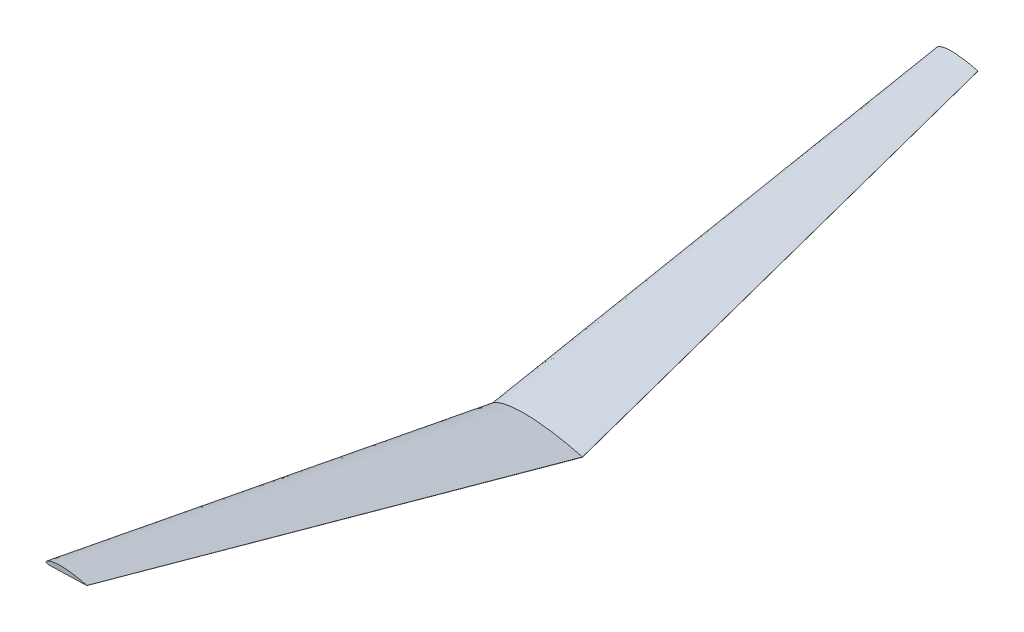
SolidWorks part; units mm, degrees
ref_plane "Front Plane" through (0, 0, 0) normal (0, 0, 1) x (1, 0, 0)
ref_plane "Top Plane" through (0, 0, 0) normal (0, 1, 0) x (1, 0, 0)
ref_plane "Right Plane" through (0, 0, 0) normal (1, 0, 0) x (0, 0, -1)
curve "Curve1"
  spline degree 3 poles (25.4, 0.033, 0) (24.9771, 0.1481, 0) (24.1334, 0.3778, 0) (22.4431, 0.7955, 0) (20.3293, 1.2569, 0) (17.7869, 1.7118, 0) (15.2464, 2.0846, 0) (12.7045, 2.3505, 0) (10.1628, 2.5164, 0) (8.041, 2.5181, 0) (6.3469, 2.4009, 0) (5.0745, 2.2465, 0) (3.7995, 2.0188, 0) (2.7428, 1.745, 0) (1.8961, 1.4685, 0) (1.2577, 1.2074, 0) (0.7129, 0.9251, 0) (0.2401, 0.5874, 0) (-0.1715, 0.0442, 0) (0.2727, -0.3711, 0) (0.7261, -0.5342, 0) (1.266, -0.6443, 0) (1.9036, -0.7002, 0) (2.7513, -0.7398, 0) (3.8103, -0.7368, 0) (5.0806, -0.7013, 0) (6.3499, -0.6336, 0) (8.0433, -0.5544, 0) (10.1596, -0.4528, 0) (12.7001, -0.3574, 0) (15.2397, -0.2514, 0) (17.7796, -0.1611, 0) (20.3198, -0.0947, 0) (22.4366, -0.061, 0) (24.13, -0.0388, 0) (24.9767, -0.035, 0) (25.4, -0.033, 0) knots 0 0 0 0 0.025305 0.050488 0.10052 0.150191 0.199587 0.24874 0.297716 0.346601 0.371103 0.395726 0.42057 0.445825 0.458702 0.47192 0.485786 0.493461 0.506863 0.516148 0.522766 0.535269 0.547551 0.559786 0.584229 0.608681 0.633151 0.657622 0.706558 0.755482 0.804406 0.85332 0.902221 0.951113 0.975557 1 1 1 1
sketch "Sketch1" plane through (0, 0, 0) normal (0, 0, 1) x (1, 0, 0)
  arc A0 (100.041, 0.1301) -> (100.041, -0.1301) centre (100.0005, 0) cw
  spline S1 degree 3 poles (100.041, 0.1301) (98.3753, 0.5835) (95.0521, 1.4881) (88.3947, 3.133) (80.0695, 4.9504) (70.0557, 6.7419) (60.0498, 8.2104) (50.0382, 9.2579) (40.0275, 9.9112) (31.6705, 9.9178) (24.9979, 9.4562) (19.9867, 8.8481) (14.9646, 7.9514) (10.803, 6.873) (7.4681, 5.7839) (4.9535, 4.7556) (2.8079, 3.6437) (0.9456, 2.3135) (-0.6757, 0.1743) (1.0742, -1.4618) (2.8598, -2.104) (4.9863, -2.5375) (7.4977, -2.7579) (10.8364, -2.9138) (15.0072, -2.9022) (20.0104, -2.7622) (25.01, -2.4956) (31.6794, -2.1837) (40.0148, -1.7834) (50.0208, -1.4075) (60.0235, -0.9901) (70.0273, -0.6346) (80.0318, -0.3732) (88.3693, -0.2404) (95.0388, -0.153) (98.3736, -0.1377) (100.041, -0.1301) knots 0 0 0 0 0.025305 0.050488 0.10052 0.150191 0.199587 0.24874 0.297716 0.346601 0.371103 0.395726 0.42057 0.445825 0.458702 0.47192 0.485786 0.493461 0.506863 0.516148 0.522766 0.535269 0.547551 0.559786 0.584229 0.608681 0.633151 0.657622 0.706558 0.755482 0.804406 0.85332 0.902221 0.951113 0.975557 1 1 1 1
ref_plane "Plane1" through (0, 0, 490.8136) normal (0, 0, 1) x (1, 0, 0)
sketch "Sketch2" plane through (0, 0, 490.8136) normal (0, 0, 1) x (1, 0, 0)
  arc A0 (45, 95.463) -> (45, 95.346) centre (44.9843, 95.4045) cw
  spline S1 degree 3 poles (45, 95.463) (44.2508, 95.6669) (42.7559, 96.0739) (39.7613, 96.8138) (36.0165, 97.6313) (31.5122, 98.4371) (27.0113, 99.0977) (22.508, 99.5688) (18.005, 99.8627) (14.2459, 99.8657) (11.2444, 99.658) (8.9903, 99.3845) (6.7313, 98.9812) (4.8594, 98.4961) (3.3593, 98.0062) (2.2282, 97.5437) (1.2631, 97.0435) (0.4253, 96.4452) (-0.3039, 95.4829) (0.4832, 94.747) (1.2864, 94.4581) (2.2429, 94.2631) (3.3726, 94.164) (4.8744, 94.0938) (6.7505, 94.0991) (9.001, 94.162) (11.2499, 94.2819) (14.2499, 94.4222) (17.9993, 94.6023) (22.5001, 94.7714) (26.9995, 94.9591) (31.4994, 95.119) (35.9996, 95.2366) (39.7499, 95.2964) (42.7499, 95.3357) (44.25, 95.3426) (45, 95.346) knots 0 0 0 0 0.025305 0.050488 0.10052 0.150191 0.199587 0.24874 0.297716 0.346601 0.371103 0.395726 0.42057 0.445825 0.458702 0.47192 0.485786 0.493461 0.506863 0.516148 0.522766 0.535269 0.547551 0.559786 0.584229 0.608681 0.633151 0.657622 0.706558 0.755482 0.804406 0.85332 0.902221 0.951113 0.975557 1 1 1 1
  point P1 (0, 95.4045)
  dimension "D1" = 0.0606
  dimension "D2" = 95.4045
loft "Loft1" add profiles "Sketch2", "Sketch1" connector at (45, 95.463, 490.8136) connector at (100.041, 0.1301, 0)
mirror "Mirror1" about plane through (0.3078, 1.3112, 0) normal (0, 0, -1) of "Loft1"
